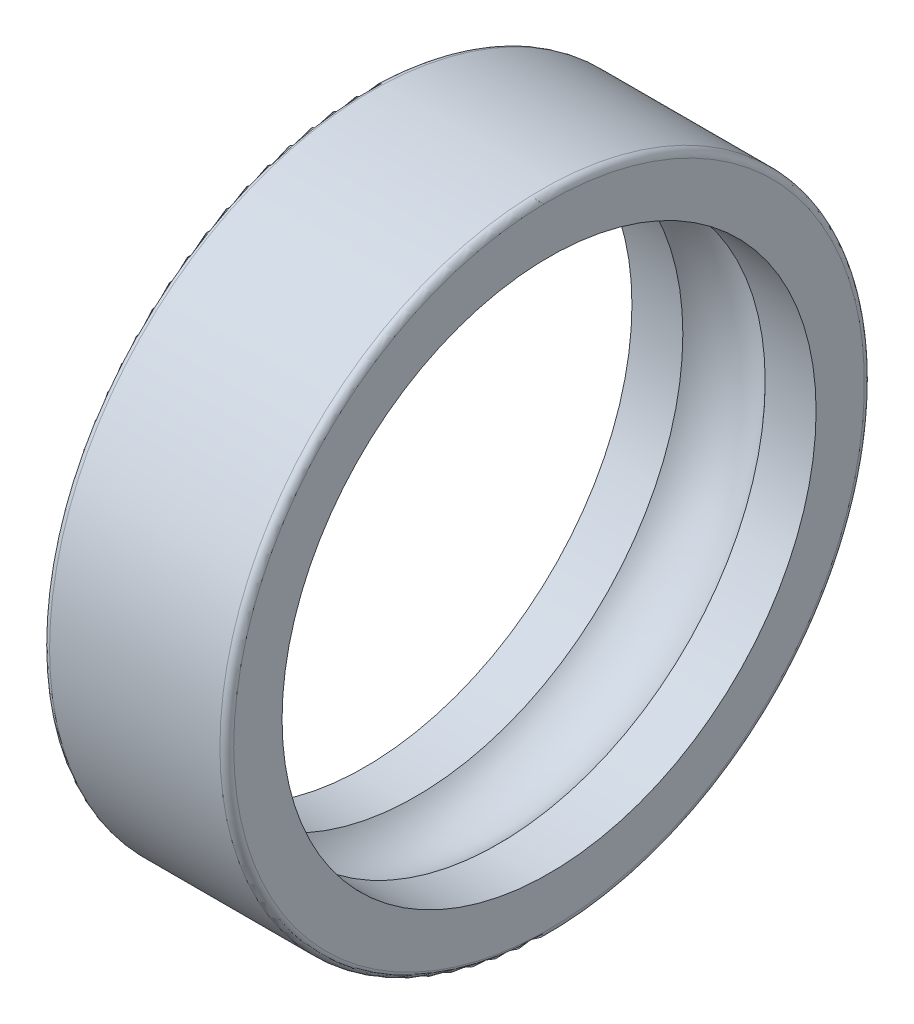
SolidWorks part; units mm, degrees
ref_plane "Plan1" through (0, 0, 0) normal (0, 0, 1) x (1, 0, 0)
ref_plane "Plan2" through (0, 0, 0) normal (0, 1, 0) x (1, 0, 0)
ref_plane "Plan3" through (0, 0, 0) normal (1, 0, 0) x (0, 0, -1)
ref_axis "Axe1" through (-50, 0, 0) along (1, 0, 0)
sketch "Esquisse1" plane through (0, 0, 0) normal (0, 1, 0) x (1, 0, 0)
  line L0 (0, 13.7) -> (0, 6.3) construction
  line L1 (8, 11.6) -> (0, 11.6) construction
  line L2 (8, 13.7) -> (8, 6.3) construction
  line L3 (0.3, 14) -> (7.7, 14) construction
  line L4 (0, 13.7) -> (0, 11.6)
  line L5 (8, 11.6) -> (5.7889, 11.6)
  line L6 (0, 0) -> (12, 0) construction
  line L7 (-50, 0) -> (200, 0) construction
  line L8 (8, 13.7) -> (8, 11.6)
  line L9 (0.3, 14) -> (7.7, 14)
  line L10 (2.2111, 11.6) -> (0, 11.6)
  arc A0 (0.3, 14) -> (0, 13.7) centre (0.3, 13.7) ccw construction
  circle A1 centre (4, 10) radius 2.4 construction
  arc A3 (8, 13.7) -> (7.7, 14) centre (7.7, 13.7) ccw construction
  arc A4 (0.3, 14) -> (0, 13.7) centre (0.3, 13.7) ccw
  arc A5 (5.7889, 11.6) -> (2.2111, 11.6) centre (4, 10) ccw
  arc A6 (8, 13.7) -> (7.7, 14) centre (7.7, 13.7) ccw
revolve "Base-Révolution" add sketch "Esquisse1" angle 360 about L6
